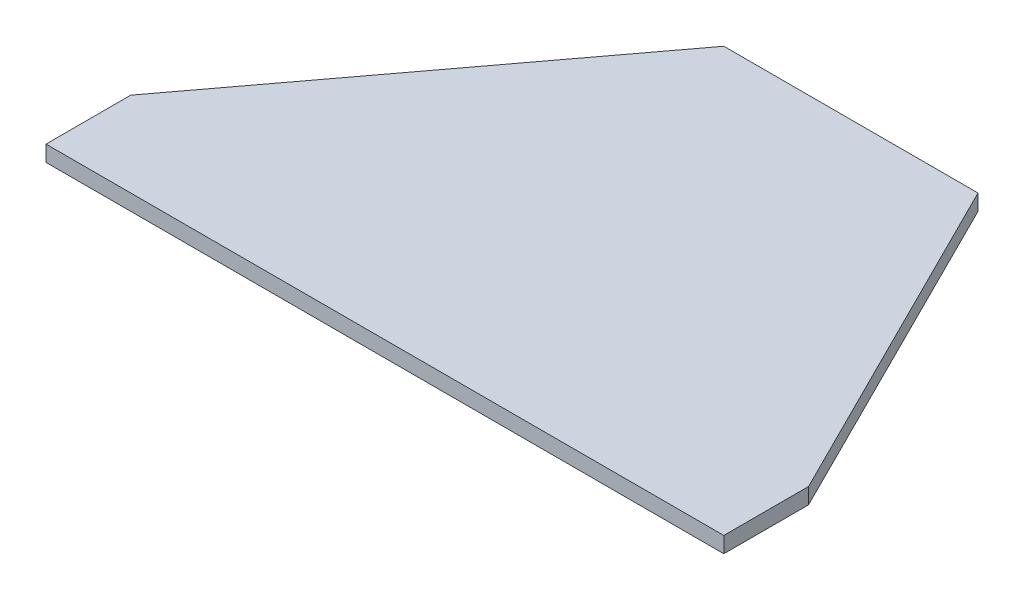
SolidWorks part; units mm, degrees
ref_plane "Front Plane" through (0, 0, 0) normal (0, 0, 1) x (1, 0, 0)
ref_plane "Top Plane" through (0, 0, 0) normal (0, 1, 0) x (1, 0, 0)
ref_plane "Right Plane" through (0, 0, 0) normal (1, 0, 0) x (0, 0, -1)
sketch "Sketch1" plane through (0, 0, 0) normal (0, 1, 0) x (1, 0, 0)
  line L0 (0, 0) -> (0, 25.4)
  line L1 (0, 25.4) -> (76.2, 127)
  line L2 (76.2, 127) -> (152.4, 127)
  line L3 (152.4, 127) -> (203.2, 25.4)
  line L4 (203.2, 25.4) -> (203.2, 0)
  line L5 (203.2, 0) -> (0, 0)
  line L6 (0, 25.4) -> (0, 127) construction
  line L7 (0, 127) -> (76.2, 127) construction
  dimension "D1" = 203.2
  dimension "D2" = 25.4
  dimension "D3" = 76.2
  dimension "D4" = 101.6
  dimension "D5" = 76.2
extrude "Boss-Extrude1" add sketch "Sketch1" along normal blind 2.3813 and the other way blind 2.3813 contours L3 L4 L5 L0 L1 L2
equation "\"Root Chord\"= 8"
equation "\"Tip Chord\"= 3"
equation "\"Height\"=4"
equation "\"Sweep Length\"= 3"
equation "\"Fin Thickness\"= 3 / 16"
equation "\"Bevel Depth\"= 1 / 16"
equation "\"Bevel Width\"= 1 / 4"
equation "\"Tab Height\"= 1"
equation "\"D2@Sketch1\"=\"Tab Height\""
equation "\"D4@Sketch1\"=\"Height\""
equation "\"D5@Sketch1\"=\"Sweep Length\""
equation "\"D3@Sketch1\"=\"Tip Chord\""
equation "\"D1@Sketch1\"=\"Root Chord\""
equation "\"D1@Boss-Extrude1\"=\"Fin Thickness\"/2"
equation "\"D2@Boss-Extrude1\"=\"Fin Thickness\"/2"
equation "\"D1@Chamfer2\"=\"Bevel Depth\""
equation "\"D3@Chamfer2\"=\"Bevel Width\""
